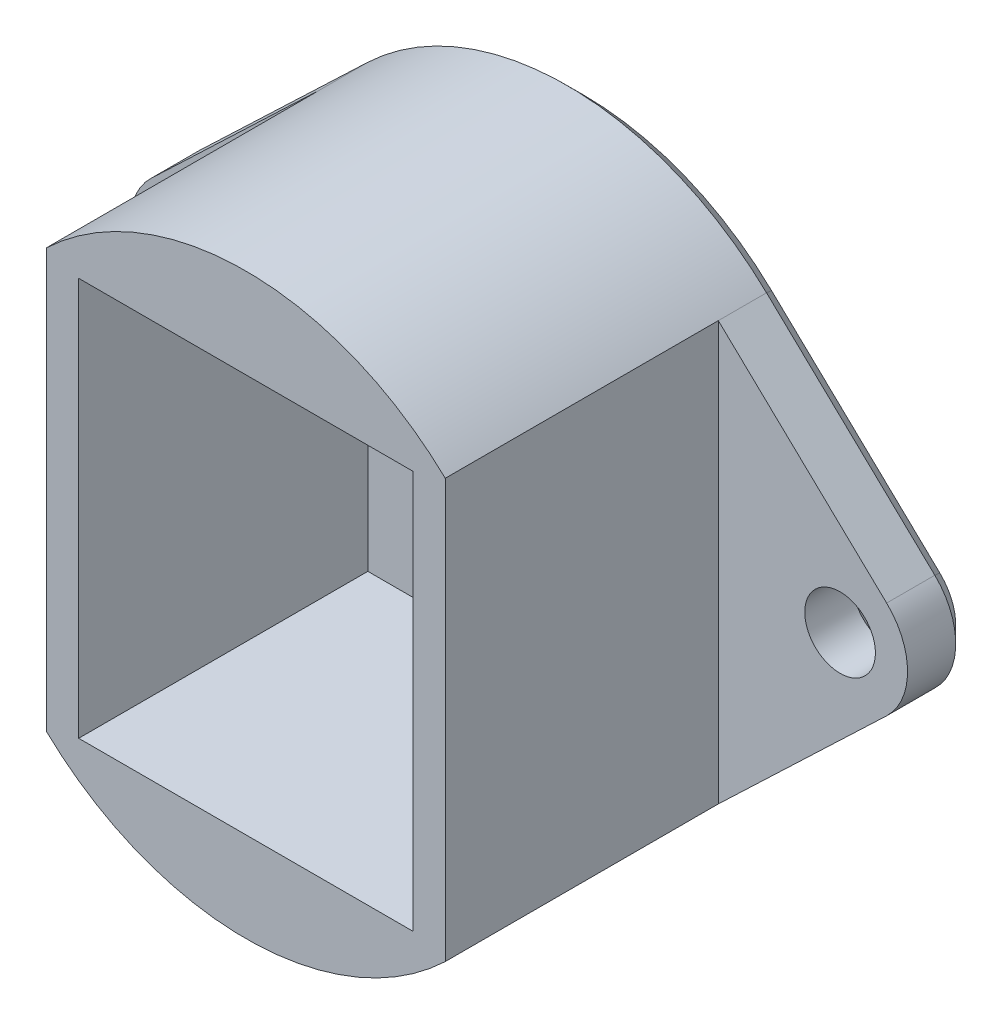
SolidWorks part; units mm, degrees
material "ABS"
ref_plane "Front" through (0, 0, 0) normal (0, 0, 1) x (1, 0, 0)
ref_plane "Top" through (0, 0, 0) normal (0, 1, 0) x (1, 0, 0)
ref_plane "Right" through (0, 0, 0) normal (1, 0, 0) x (0, 0, -1)
sketch "Эскиз2" plane through (0, 0, 0) normal (0, 0, 1) x (1, 0, 0)
  line L0 (6.21, 6.5143) -> (11.449, 1.52)
  line L1 (11.449, -1.52) -> (6.21, -6.5143)
  line L2 (-10, 0) -> (10, 0) construction
  line L3 (-6.21, -6.5143) -> (-11.449, -1.52)
  line L4 (-6.21, 6.5143) -> (-11.449, 1.52)
  line L5 (0, -9) -> (0, 9) construction
  arc A1 (11.449, 1.52) -> (11.449, -1.52) centre (10, 0) cw
  circle A2 centre (10, 0) radius 1.1
  arc A3 (6.21, -6.5143) -> (-6.21, -6.5143) centre (0, 0) cw
  circle A4 centre (-10, 0) radius 1.1
  arc A5 (-11.449, -1.52) -> (-11.449, 1.52) centre (-10, 0) cw
  arc A6 (6.21, 6.5143) -> (-6.21, 6.5143) centre (0, 0) ccw
  circle A7 centre (0, 4.5) radius 1
  circle A9 centre (0, -4.5) radius 1
  circle A10 centre (0, 0) radius 1.7
  point P12 (0, 0)
  dimension "D1" = 2.2
  dimension "D2" = 2.1
  dimension "D4" = 18
  dimension "D5" = 2
  dimension "D7" = 3.4
  dimension "D3" = 20
  dimension "D6" = 9
extrude "Бобышка-Вытянуть1" add sketch "Эскиз2" along normal blind 2
sketch "Эскиз3" plane through (0, 0, 2) normal (0, 0, 1) x (1, 0, 0)
  line L0 (-6.21, 6.5143) -> (-11.449, 1.52) construction
  line L1 (6.21, 6.5143) -> (6.21, -6.5143)
  line L2 (5.2, 6.2) -> (-5.2, 6.2)
  line L3 (5.2, 6.2) -> (5.2, -6.2)
  line L4 (5.2, -6.2) -> (-5.2, -6.2)
  line L5 (-5.2, 6.2) -> (-5.2, -6.2)
  line L6 (5.2, 6.2) -> (-5.2, -6.2) construction
  line L7 (5.2, -6.2) -> (-5.2, 6.2) construction
  line L8 (-6.21, -6.5143) -> (-6.21, 6.5143)
  arc A2 (6.21, -6.5143) -> (-6.21, -6.5143) centre (0, 0) cw
  arc A3 (-6.21, -6.5143) -> (6.21, -6.5143) centre (0, 0) ccw construction
  arc A4 (6.21, 6.5143) -> (-6.21, 6.5143) centre (0, 0) ccw
  circle A5 centre (0, 0) radius 8.092 construction
  dimension "D1" = 12.4
  dimension "D3" = 0.908
  dimension "D2" = 10.4
extrude "Бобышка-Вытянуть2" add sketch "Эскиз3" along normal offset from surface (8.5 mm away) 10.5 up to face at (0, 0, 0)
sketch "Эскиз4" plane through (0, 0, 2) normal (0, 0, 1) x (1, 0, 0)
  line L0 (5.2, -6.2) -> (5.2, 6.2) construction
  line L1 (-5.2, -6.2) -> (5.2, -6.2)
  line L2 (-5.2, -6.2) -> (-5.2, 6.2)
  line L3 (-5.2, 6.2) -> (5.2, 6.2)
  line L4 (5.2, -6.2) -> (5.2, 6.2)
  line L5 (-5.2, -6.2) -> (5.2, 6.2) construction
  line L6 (-5.2, 6.2) -> (5.2, -6.2) construction
  point P0 (0, 0)
extrude "Вырез-Вытянуть1" cut sketch "Эскиз4" against normal blind 0.5
sketch "Эскиз5" plane through (0, 0, 1.5) normal (0, 0, 1) x (1, 0, 0)
  circle A0 centre (0, 0) radius 2.25
  dimension "D1" = 4.5
extrude "Вырез-Вытянуть2" cut sketch "Эскиз5" against normal blind 0.9
chamfer "Фаска1" distance 0.5 angle 45 11 edges at (-8.9, 0, 0) (1.7, 0, 0) (11.1, 0, 0) (-8.8295, 4.0171, 0) (-12.1, 0, 0) (-8.8295, -4.0171, 0) (8.8295, -4.0171, 0) (12.1, 0, 0) (8.8295, 4.0171, 0) (0, -9, 0) (0, 9, 0)
chamfer "Фаска2" distance 0.8 angle 45 2 edges at (-1, -4.5, 0) (1, 4.5, 0)
